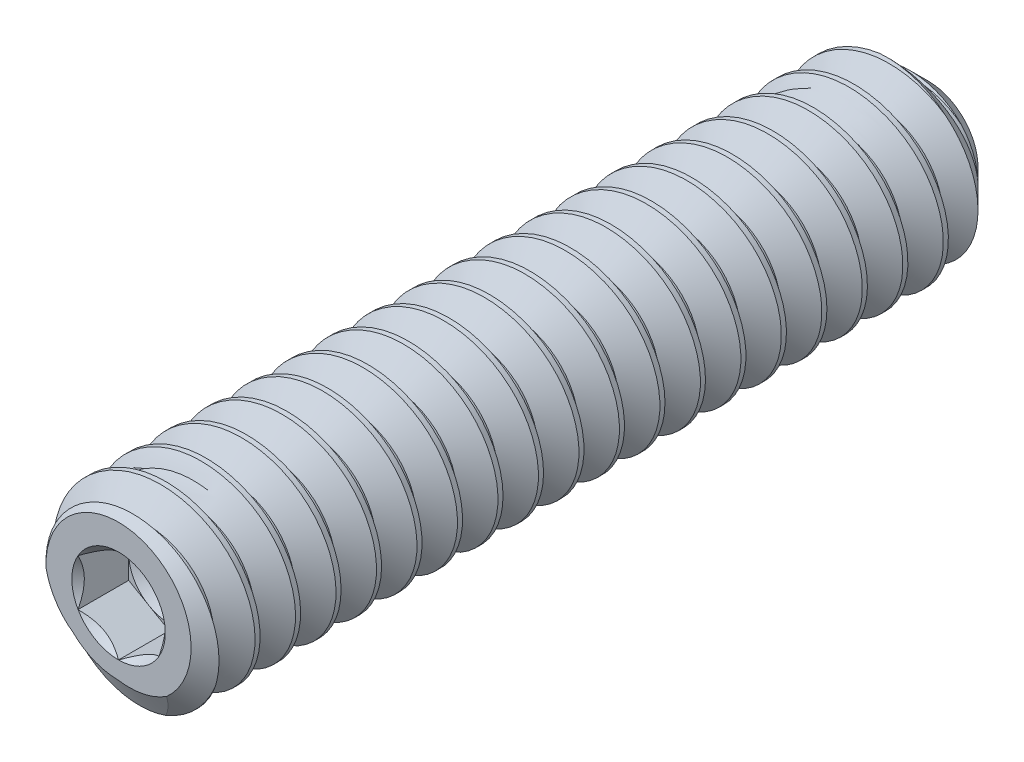
SolidWorks part; units mm, degrees
ref_plane "Front" through (0, 0, 0) normal (0, 0, 1) x (1, 0, 0)
ref_plane "Top" through (0, 0, 0) normal (0, 1, 0) x (1, 0, 0)
ref_plane "Right" through (0, 0, 0) normal (1, 0, 0) x (0, 0, -1)
sketch "Sketch22" plane through (0, 0, 0) normal (1, 0, 0) x (0, 0, -1)
  line L0 (-6.1158, 0) -> (-6.1158, 1.1379)
  line L1 (-6.1158, 1.1379) -> (-5.9166, 1.4224)
  line L2 (-5.9166, 1.4224) -> (5.9412, 1.4224)
  line L3 (5.9412, 1.4224) -> (6.5842, 0.7794)
  line L4 (6.5842, 0.7794) -> (6.1158, 0)
  line L5 (6.1158, 0) -> (-6.1158, 0)
  line L6 (6.1158, 0) -> (6.5842, 0) construction
  line L7 (6.5842, 0) -> (6.5842, 0.7794) construction
  line L8 (6.5842, -0.7794) -> (6.1158, 0) construction
  line L9 (-5.9166, -1.4224) -> (5.9412, -1.4224) construction
  dimension "Dia" = 2.8448
  dimension "Length" = 12.7
  dimension "D3" = 35
  dimension "D5" = 118
  dimension "D6" = 45
  dimension "D7" = 2.2758
revolve "Revolve1" add sketch "Sketch22" angle 360 about L6
ref_plane "Plane1" through (0, 0, -6.5842) normal (0, 0, 1) x (1, 0, 0)
sketch "Sketch27" plane through (0, 0, -6.5842) normal (0, 0, 1) x (1, 0, 0)
  circle A0 centre (0, 0) radius 1.4224 construction
  circle A1 centre (0, 0) radius 1.4224
curve "Helix/Spiral1" pitch 0.635 height 13.335 radius 1.4224 centre (0, 0, -6.5842) axis (0, 0, 1) start towards (0, 1, 0)
sketch "Sketch28" plane through (0, 0, 0) normal (1, 0, 0) x (0, 0, -1)
  line L0 (6.5842, 1.4224) -> (7.1398, 1.4224)
  line L1 (7.1398, 1.4224) -> (6.9017, 1.01)
  line L2 (6.9017, 1.01) -> (6.8223, 1.01)
  line L3 (6.8223, 1.01) -> (6.5842, 1.4224)
  line L4 (6.7032, 1.2162) -> (7.0207, 1.2162) construction
  line L6 (-5.9166, 1.4224) -> (5.9412, 1.4224) construction
  line L7 (6.5842, 1.2014) -> (6.5842, -1.2014) construction
  dimension "D1" = 0.0794
  dimension "D3" = 60
  dimension "D2" = 0.3175
sweep "Cut-Sweep2" cut profiles "Sketch28" path "Helix/Spiral1" align with end faces yes
sketch "Sketch23" plane through (0, 0, 6.1158) normal (0, 0, 1) x (1, 0, 0)
  line L1 (0, 0.7332) -> (-0.635, 0.3666)
  line L2 (-0.635, 0.3666) -> (-0.635, -0.3666)
  line L3 (-0.635, -0.3666) -> (0, -0.7332)
  line L4 (0, -0.7332) -> (0.635, -0.3666)
  line L5 (0.635, -0.3666) -> (0.635, 0.3666)
  line L6 (0.635, 0.3666) -> (0, 0.7332)
  circle A0 centre (0, 0) radius 0.635 construction
  dimension "Hex" = 1.27
extrude "Cut-Extrude10" cut sketch "Sketch23" against normal blind 0.7937
sketch "Sketch24" plane through (0, 0, 6.1158) normal (0, 0, 1) x (1, 0, 0)
  circle A0 centre (0, 0) radius 0.7332
extrude "Cut-Extrude11" cut sketch "Sketch24" against normal through all draft 45
sketch "Sketch26" plane through (0, 0, 5.3221) normal (0, 0, 1) x (1, 0, 0)
  circle A0 centre (0, 0) radius 0.635 construction
  circle A1 centre (0, 0) radius 0.635
extrude "Cut-Extrude12" cut sketch "Sketch26" against normal through all draft 60
sketch "Sketch30" plane through (0, 0, 0) normal (1, 0, 0) x (0, 0, -1)
  line L0 (-5.9166, 1.4224) -> (5.9412, 1.4224) construction
  line L1 (-6.1158, 0) -> (-6.1158, 1.1379) construction
  line L2 (6.5842, 0) -> (6.5842, 0.7794) construction
  line L3 (-5.9166, -1.4224) -> (5.9412, -1.4224) construction
  point P0 (-6.1158, 1.4224)
  point P1 (6.5842, 1.4224)
  point P2 (6.5842, -1.4224)
  point P11 (4.9967, -1.4224)
  dimension "D1" = 1.5875
sketch "Sketch31" plane through (0, 0, 0) normal (1, 0, 0) x (0, 0, -1)
  line L2 (6.1158, 0) -> (6.5842, -0.7794)
  line L3 (6.5842, 0.7794) -> (6.1158, 0)
equation "\"D7@Sketch22\"=\"Dia@Sketch22\"*.8"
equation "\"D1@Sketch28\" = \"D4@Helix/Spiral1\" * .125"
equation "\"D3@Helix/Spiral1\" = \"Length@Sketch22\" + \"D4@Helix/Spiral1\""
equation "\"D1@Sketch30\" = \"D4@Helix/Spiral1\" * 2.5"
equation "\"hex Depth@Cut-Extrude10\" = \"Hex@Sketch23\" * .625"
equation "\"D2@Sketch28\" = \"D4@Helix/Spiral1\" * .5"
